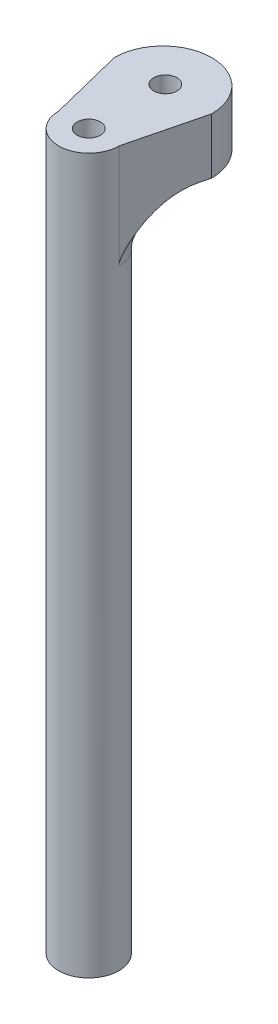
SolidWorks part; units mm, degrees
note: '?' marks a value the reader was unsure of.
ref_plane "Front Plane" through (0, 0, 0) normal (0, 0, 1) x (1, 0, 0)
ref_plane "Top Plane" through (0, 0, 0) normal (0, 1, 0) x (1, 0, 0)
ref_plane "Right Plane" through (0, 0, 0) normal (1, 0, 0) x (0, 0, -1)
sketch "Sketch1" plane through (0, 0, 0) normal (0, 1, 0) x (1, 0, 0)
  line L5 (-74.7372, 53.6031) -> (-82.7372, 53.6031) construction
  line L14 (-80.1916, 56.1031) -> (-76.8139, 56.1031)
  line L15 (-80.1916, 51.1031) -> (-76.8139, 51.1031)
  line L16 (-72.6606, 56.1031) -> (-69.2829, 56.1031)
  line L17 (-72.6606, 51.1031) -> (-69.2829, 51.1031)
  circle A0 centre (-74.7372, 53.6031) radius 6 construction
  arc A1 (-76.8139, 56.1031) -> (-72.6606, 56.1031) centre (-74.7372, 53.6031) cw
  arc A2 (-72.6606, 51.1031) -> (-76.8139, 51.1031) centre (-74.7372, 53.6031) cw
  arc A3 (-69.2829, 56.1031) -> (-69.2829, 51.1031) centre (-74.7372, 53.6031) cw
  arc A4 (-80.1916, 56.1031) -> (-80.1909, 51.1016) centre (-74.7372, 53.6031) ccw
  arc A5 (-76.8139, 51.1031) -> (-76.8139, 56.1031) centre (-74.7372, 53.6031) cw
  circle A6 centre (-74.7372, 53.6031) radius 3.25 construction
  arc A7 (-72.6606, 56.1031) -> (-72.6606, 51.1031) centre (-74.7372, 53.6031) cw
  circle A10 centre (-74.7372, 53.6031) radius 8 construction
  dimension "D1" = 6.5
  dimension "D2" = 12
  dimension "D3" = 16
  dimension "D4" = 2.5
  dimension "D5" = 2.5
extrude "Boss-Extrude1" add sketch "Sketch1" along normal blind 5 contours L14 A4 L15 A2 L17 A3 L16 A1
sketch "Sketch4" plane through (0, 5, 0) normal (0, 1, 0) x (1, 0, 0)
  circle A0 centre (-74.7372, 53.6031) radius 3.25 construction
  circle A1 centre (-74.7372, 53.6031) radius 3.25
extrude "Boss-Extrude2" add sketch "Sketch4" along normal blind 4
sketch "Sketch5" plane through (0, 9, 0) normal (0, 1, 0) x (1, 0, 0)
  line L0 (-80.1916, 51.1031) -> (-76.8139, 51.1031) construction
  line L1 (-72.6606, 51.1031) -> (-69.2829, 51.1031) construction
  line L2 (-72.6606, 56.1031) -> (-69.2829, 56.1031) construction
  line L3 (-80.1916, 56.1031) -> (-76.8139, 56.1031) construction
  line L4 (-80.1916, 51.1031) -> (-76.8139, 51.1031)
  line L5 (-72.6606, 51.1031) -> (-69.2829, 51.1031)
  line L6 (-72.6606, 56.1031) -> (-69.2829, 56.1031)
  line L7 (-80.1916, 56.1031) -> (-76.8139, 56.1031)
  arc A0 (-76.8139, 51.1031) -> (-72.6606, 51.1031) centre (-74.7372, 53.6031) ccw construction
  arc A1 (-69.2829, 51.1031) -> (-69.2829, 56.1031) centre (-74.7372, 53.6031) ccw construction
  arc A2 (-72.6606, 56.1031) -> (-76.8139, 56.1031) centre (-74.7372, 53.6031) ccw construction
  arc A3 (-80.1916, 56.1031) -> (-80.1909, 51.1016) centre (-74.7372, 53.6031) ccw construction
  arc A4 (-76.8139, 51.1031) -> (-72.6606, 51.1031) centre (-74.7372, 53.6031) ccw
  arc A5 (-69.2829, 51.1031) -> (-69.2829, 56.1031) centre (-74.7372, 53.6031) ccw
  arc A6 (-72.6606, 56.1031) -> (-76.8139, 56.1031) centre (-74.7372, 53.6031) ccw
  arc A7 (-80.1916, 56.1031) -> (-80.1909, 51.1016) centre (-74.7372, 53.6031) ccw
  arc A8 (-76.8139, 51.1031) -> (-76.786, 56.126) centre (-74.7372, 53.6031) cw
  arc A9 (-72.6606, 56.1031) -> (-72.6606, 51.1031) centre (-74.7372, 53.6031) cw
  circle M1 centre (-74.7372, 53.6031) radius 3.25
extrude "Boss-Extrude3" add sketch "Sketch5" along normal blind 2 contours A6 A7 M1
sketch "Sketch6" plane through (0, 11, 0) normal (0, 1, 0) x (1, 0, 0)
  circle A1 centre (-74.7372, 53.6031) radius 3.25
extrude "Boss-Extrude4" add sketch "Sketch6" along normal blind 60
sketch "Sketch7" plane through (0, 71, 0) normal (0, 1, 0) x (1, 0, 0)
  line L0 (-74.7372, 53.6031) -> (-82.7372, 53.6031) construction
  line L1 (-77.9872, 53.6031) -> (-82.7372, 53.6031) construction
  line L4 (-77.9872, 53.6031) -> (-77.9872, 61.6031)
  line L6 (-71.4872, 53.6031) -> (-71.4872, 61.6031)
  circle A0 centre (-74.7372, 53.6031) radius 3.25 construction
  arc A1 (-77.9872, 53.6031) -> (-71.4872, 53.6031) centre (-74.7372, 53.6031) ccw
  arc A2 (-71.4872, 61.6031) -> (-77.9872, 61.6031) centre (-74.7372, 61.6031) ccw
  dimension "D1" = 8
extrude "Boss-Extrude5" add sketch "Sketch7" along normal blind 6
fillet "Fillet2" [suppressed] radius 0.4
fillet "Fillet4" [suppressed] radius 1.2
sketch "Sketch8" plane through (0, 77, 0) normal (0, 1, 0) x (1, 0, 0)
  circle A0 centre (-74.7372, 61.8531) radius 1.25
  arc A1 (-71.4872, 61.6031) -> (-77.9872, 61.6031) centre (-74.7372, 61.6031) ccw construction
  point P2 (-74.7372, 64.8531)
  dimension "D1" = 2.5
  dimension "D2" = 3
extrude "Cut-Extrude1" cut sketch "Sketch8" against normal through all contours A0
sketch "Sketch9" plane through (0, 77, 0) normal (0, 1, 0) x (1, 0, 0)
  line L0 (-71.4872, 53.6031) -> (-71.4872, 61.6031) construction
  line L1 (-77.9872, 61.6031) -> (-77.9872, 53.6031) construction
  line L2 (-71.4872, 53.6031) -> (-71.4872, 61.6031)
  line L3 (-77.9872, 61.6031) -> (-77.9872, 53.6031)
  line L4 (-71.4872, 53.6031) -> (-69.4872, 61.6031)
  line L5 (-77.9872, 53.6031) -> (-79.9872, 61.6031)
  line L6 (-69.4872, 53.6031) -> (-69.4872, 61.6031) construction
  line L7 (-79.9872, 61.6031) -> (-79.9872, 53.6031) construction
  arc A0 (-71.4872, 61.6031) -> (-77.9872, 61.6031) centre (-74.7372, 61.6031) ccw construction
  arc A1 (-71.4872, 61.6031) -> (-77.9872, 61.6031) centre (-74.7372, 61.6031) ccw
  arc A2 (-69.4872, 61.6031) -> (-79.9872, 61.6031) centre (-74.7372, 61.6031) ccw
  dimension "D1" = 2
extrude "Boss-Extrude6" add sketch "Sketch9" against normal blind 6
ref_axis "Axis1" through (-74.7372, 77, -53.6031) along (0, -1, 0)?
ref_plane "Plane2" through (-74.7372, 0, 0) normal (1, 0, 0) x (0, 0, -1)
other "Half Cut 1" [suppressed]
other "Half Cut 2" [suppressed]
fillet "Fillet5" radius 5.2 1 edges
sketch "Sketch10" plane through (0, 0, 0) normal (0, -1, 0) x (1, 0, 0)
  circle A0 centre (-74.7372, -53.6031) radius 1.25
  dimension "D1" = 2.5
extrude "Cut-Extrude2" cut sketch "Sketch10" against normal through all contours A0
